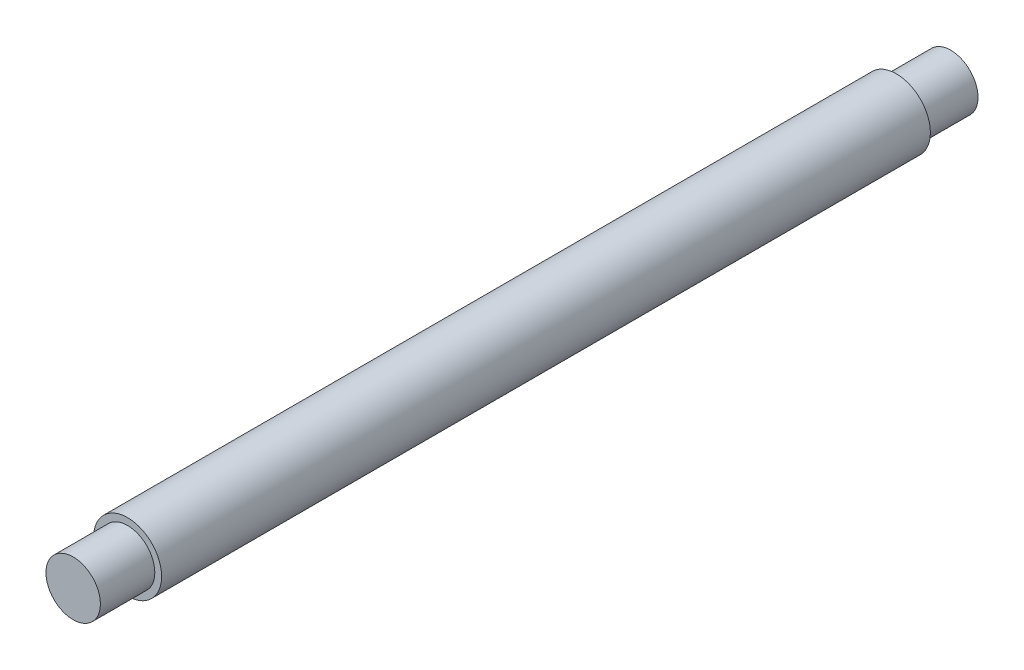
SolidWorks part; units mm, degrees
ref_plane "Front Plane" through (0, 0, 0) normal (0, 0, 1) x (1, 0, 0)
ref_plane "Top Plane" through (0, 0, 0) normal (0, 1, 0) x (1, 0, 0)
ref_plane "Right Plane" through (0, 0, 0) normal (1, 0, 0) x (0, 0, -1)
sketch "Sketch1" plane through (0, 0, 0) normal (0, 0, 1) x (1, 0, 0)
  circle A0 centre (0, 0) radius 5
  circle A1 centre (0, 0) radius 4
  point P2 (0, 0)
  point P5 (0, 0)
  dimension "D1" = 10
  dimension "D2" = 8
extrude "Boss-Extrude1" add sketch "Sketch1" along normal mid plane 113 contours A0 A1 | A1 region at (-4.8586, 0, 0) region at (0, 0, 0)
extrude "Boss-Extrude2" add sketch "Sketch1<3>" along normal mid plane 129 contours A1
sketch "Sketch1<3>" plane through (0, 0, 0) normal (0, 0, 1) x (1, 0, 0) same geometry as "Sketch1"
